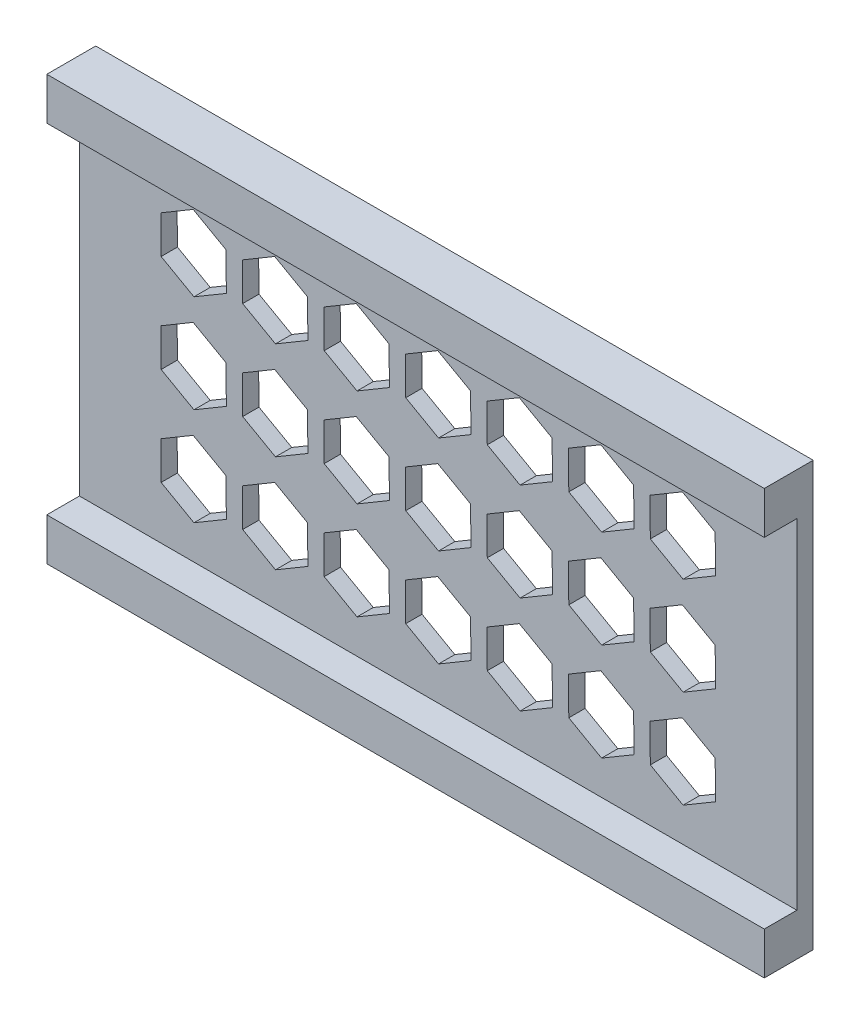
SolidWorks part; units mm, degrees
ref_plane "Front" through (0, 0, 0) normal (0, 0, 1) x (1, 0, 0)
ref_plane "Top" through (0, 0, 0) normal (0, 1, 0) x (1, 0, 0)
ref_plane "Right" through (0, 0, 0) normal (1, 0, 0) x (0, 0, -1)
sketch "Эскиз3" plane through (0, 0, 0) normal (0, 0, 1) x (1, 0, 0)
  line L0 (34.9411, 5.8743) -> (24.8833, 11.5464)
  line L1 (9.9411, 5.8743) -> (-0.1167, 11.5464)
  line L2 (110, -65) -> (-110, -65)
  line L3 (110, -65) -> (110, 65)
  line L4 (110, 65) -> (-110, 65)
  line L5 (-110, -65) -> (-110, 65)
  line L6 (110, -65) -> (-110, 65) construction
  line L7 (110, 65) -> (-110, -65) construction
  line L8 (-0.1167, 11.5464) -> (-10.0579, 5.6721)
  line L9 (-10.0579, 5.6721) -> (-9.9411, -5.8743)
  line L10 (-9.9411, -5.8743) -> (0.1167, -11.5464)
  line L11 (0.1167, -11.5464) -> (10.0579, -5.6721)
  line L12 (10.0579, -5.6721) -> (9.9411, 5.8743)
  line L13 (24.8833, 11.5464) -> (14.9421, 5.6721)
  line L14 (14.9421, 5.6721) -> (15.0589, -5.8743)
  line L15 (15.0589, -5.8743) -> (25.1167, -11.5464)
  line L16 (25.1167, -11.5464) -> (35.0579, -5.6721)
  line L17 (35.0579, -5.6721) -> (34.9411, 5.8743)
  line L18 (59.9411, 5.8743) -> (49.8833, 11.5464)
  line L19 (49.8833, 11.5464) -> (39.9421, 5.6721)
  line L20 (39.9421, 5.6721) -> (40.0589, -5.8743)
  line L21 (40.0589, -5.8743) -> (50.1167, -11.5464)
  line L22 (50.1167, -11.5464) -> (60.0579, -5.6721)
  line L23 (60.0579, -5.6721) -> (59.9411, 5.8743)
  line L24 (84.9411, 5.8743) -> (74.8833, 11.5464)
  line L25 (74.8833, 11.5464) -> (64.9421, 5.6721)
  line L26 (64.9421, 5.6721) -> (65.0589, -5.8743)
  line L27 (65.0589, -5.8743) -> (75.1167, -11.5464)
  line L28 (75.1167, -11.5464) -> (85.0579, -5.6721)
  line L29 (85.0579, -5.6721) -> (84.9411, 5.8743)
  line L30 (-15.0602, 5.8743) -> (-25.118, 11.5464)
  line L31 (-25.118, 11.5464) -> (-35.0591, 5.6721)
  line L32 (-35.0591, 5.6721) -> (-34.9424, -5.8743)
  line L33 (-34.9424, -5.8743) -> (-24.8845, -11.5464)
  line L34 (-24.8845, -11.5464) -> (-14.9434, -5.6721)
  line L35 (-14.9434, -5.6721) -> (-15.0602, 5.8743)
  line L36 (-40.0614, 5.8743) -> (-50.1193, 11.5464)
  line L37 (-50.1193, 11.5464) -> (-60.0604, 5.6721)
  line L38 (-60.0604, 5.6721) -> (-59.9437, -5.8743)
  line L39 (-59.9437, -5.8743) -> (-49.8858, -11.5464)
  line L40 (-49.8858, -11.5464) -> (-39.9447, -5.6721)
  line L41 (-39.9447, -5.6721) -> (-40.0614, 5.8743)
  line L42 (-65.0627, 5.8743) -> (-75.1206, 11.5464)
  line L43 (-75.1206, 11.5464) -> (-85.0617, 5.6721)
  line L44 (-85.0617, 5.6721) -> (-84.945, -5.8743)
  line L45 (-84.945, -5.8743) -> (-74.8871, -11.5464)
  line L46 (-74.8871, -11.5464) -> (-64.946, -5.6721)
  line L47 (-64.946, -5.6721) -> (-65.0627, 5.8743)
  line L48 (-65.0627, 35.8743) -> (-75.1206, 41.5464)
  line L49 (-75.1206, 41.5464) -> (-85.0617, 35.6721)
  line L50 (-85.0617, 35.6721) -> (-84.945, 24.1257)
  line L51 (-84.945, 24.1257) -> (-74.8871, 18.4536)
  line L52 (-74.8871, 18.4536) -> (-64.946, 24.3279)
  line L53 (-64.946, 24.3279) -> (-65.0627, 35.8743)
  line L54 (-40.0614, 35.8743) -> (-50.1193, 41.5464)
  line L55 (-50.1193, 41.5464) -> (-60.0604, 35.6721)
  line L56 (-60.0604, 35.6721) -> (-59.9437, 24.1257)
  line L57 (-59.9437, 24.1257) -> (-49.8858, 18.4536)
  line L58 (-49.8858, 18.4536) -> (-39.9447, 24.3279)
  line L59 (-39.9447, 24.3279) -> (-40.0614, 35.8743)
  line L60 (-15.0602, 35.8743) -> (-25.118, 41.5464)
  line L61 (-25.118, 41.5464) -> (-35.0591, 35.6721)
  line L62 (-35.0591, 35.6721) -> (-34.9424, 24.1257)
  line L63 (-34.9424, 24.1257) -> (-24.8845, 18.4536)
  line L64 (-24.8845, 18.4536) -> (-14.9434, 24.3279)
  line L65 (-14.9434, 24.3279) -> (-15.0602, 35.8743)
  line L66 (9.9411, 35.8743) -> (-0.1167, 41.5464)
  line L67 (-0.1167, 41.5464) -> (-10.0579, 35.6721)
  line L68 (-10.0579, 35.6721) -> (-9.9411, 24.1257)
  line L69 (-9.9411, 24.1257) -> (0.1167, 18.4536)
  line L70 (0.1167, 18.4536) -> (10.0579, 24.3279)
  line L71 (10.0579, 24.3279) -> (9.9411, 35.8743)
  line L72 (34.9411, 35.8743) -> (24.8833, 41.5464)
  line L73 (24.8833, 41.5464) -> (14.9421, 35.6721)
  line L74 (14.9421, 35.6721) -> (15.0589, 24.1257)
  line L75 (15.0589, 24.1257) -> (25.1167, 18.4536)
  line L76 (25.1167, 18.4536) -> (35.0579, 24.3279)
  line L77 (35.0579, 24.3279) -> (34.9411, 35.8743)
  line L78 (59.9411, 35.8743) -> (49.8833, 41.5464)
  line L79 (49.8833, 41.5464) -> (39.9421, 35.6721)
  line L80 (39.9421, 35.6721) -> (40.0589, 24.1257)
  line L81 (40.0589, 24.1257) -> (50.1167, 18.4536)
  line L82 (50.1167, 18.4536) -> (60.0579, 24.3279)
  line L83 (60.0579, 24.3279) -> (59.9411, 35.8743)
  line L84 (84.9411, 35.8743) -> (74.8833, 41.5464)
  line L85 (74.8833, 41.5464) -> (64.9421, 35.6721)
  line L86 (64.9421, 35.6721) -> (65.0589, 24.1257)
  line L87 (65.0589, 24.1257) -> (75.1167, 18.4536)
  line L88 (75.1167, 18.4536) -> (85.0579, 24.3279)
  line L89 (85.0579, 24.3279) -> (84.9411, 35.8743)
  line L90 (-40.0614, -24.1257) -> (-50.1193, -18.4536)
  line L91 (-50.1193, -18.4536) -> (-60.0604, -24.3279)
  line L92 (-60.0604, -24.3279) -> (-59.9437, -35.8743)
  line L93 (-59.9437, -35.8743) -> (-49.8858, -41.5464)
  line L94 (-49.8858, -41.5464) -> (-39.9447, -35.6721)
  line L95 (-39.9447, -35.6721) -> (-40.0614, -24.1257)
  line L96 (-15.0602, -24.1257) -> (-25.118, -18.4536)
  line L97 (-25.118, -18.4536) -> (-35.0591, -24.3279)
  line L98 (-35.0591, -24.3279) -> (-34.9424, -35.8743)
  line L99 (-34.9424, -35.8743) -> (-24.8845, -41.5464)
  line L100 (-24.8845, -41.5464) -> (-14.9434, -35.6721)
  line L101 (-14.9434, -35.6721) -> (-15.0602, -24.1257)
  line L102 (-65.0627, -24.1257) -> (-75.1206, -18.4536)
  line L103 (-75.1206, -18.4536) -> (-85.0617, -24.3279)
  line L104 (-85.0617, -24.3279) -> (-84.945, -35.8743)
  line L105 (-84.945, -35.8743) -> (-74.8871, -41.5464)
  line L106 (-74.8871, -41.5464) -> (-64.946, -35.6721)
  line L107 (-64.946, -35.6721) -> (-65.0627, -24.1257)
  line L108 (9.9411, -24.1257) -> (-0.1167, -18.4536)
  line L109 (-0.1167, -18.4536) -> (-10.0579, -24.3279)
  line L110 (-10.0579, -24.3279) -> (-9.9411, -35.8743)
  line L111 (-9.9411, -35.8743) -> (0.1167, -41.5464)
  line L112 (0.1167, -41.5464) -> (10.0579, -35.6721)
  line L113 (10.0579, -35.6721) -> (9.9411, -24.1257)
  line L114 (34.9411, -24.1257) -> (24.8833, -18.4536)
  line L115 (24.8833, -18.4536) -> (14.9421, -24.3279)
  line L116 (14.9421, -24.3279) -> (15.0589, -35.8743)
  line L117 (15.0589, -35.8743) -> (25.1167, -41.5464)
  line L118 (25.1167, -41.5464) -> (35.0579, -35.6721)
  line L119 (35.0579, -35.6721) -> (34.9411, -24.1257)
  line L120 (59.9411, -24.1257) -> (49.8833, -18.4536)
  line L121 (49.8833, -18.4536) -> (39.9421, -24.3279)
  line L122 (39.9421, -24.3279) -> (40.0589, -35.8743)
  line L123 (40.0589, -35.8743) -> (50.1167, -41.5464)
  line L124 (50.1167, -41.5464) -> (60.0579, -35.6721)
  line L125 (60.0579, -35.6721) -> (59.9411, -24.1257)
  line L126 (85.0579, -35.6721) -> (84.9411, -24.1257)
  line L127 (75.1167, -41.5464) -> (85.0579, -35.6721)
  line L128 (65.0589, -35.8743) -> (75.1167, -41.5464)
  line L129 (64.9421, -24.3279) -> (65.0589, -35.8743)
  line L130 (74.8833, -18.4536) -> (64.9421, -24.3279)
  line L131 (84.9411, -24.1257) -> (74.8833, -18.4536)
  line L132 (-40.0614, 5.8743) -> (-40.0614, -24.1257) construction
  line L133 (-110, 52) -> (110, 52)
  line L135 (0, 0) -> (110, 0) construction
  line L136 (-110, -52) -> (110, -52)
  circle A0 centre (0, 0) radius 10 construction
  point P1 (0, 0)
  point P6 (-9.9995, 29.8989)
  dimension "D3" = 20
  dimension "D1" = 220
  dimension "D2" = 130
  dimension "D4" = 11.5464
  dimension "D6" = 14.9987
  dimension "D8" = 15
  dimension "D10" = 9.9995
  dimension "D11" = 11.5464
  dimension "D12" = 64.6967
  dimension "D13" = 30
  dimension "D14" = 220
  dimension "D15" = 52
  dimension "D5" = 4
  dimension "D7" = 4
  dimension "D9" = 2
extrude "Бобышка-Вытянуть1" add sketch "Эскиз3" along normal blind 5 contours L5 L4 L3 L2
extrude "Вырез-Вытянуть1" cut sketch "Эскиз3<3>" along normal through all contours L28 L29 L24 L25 L26 L27 | L22 L23 L18 L19 L20 L21 | L124 L125 L120 L121 L122 L123 | L118 L119 L114 L115 L116 L117 | L16 L17 L0 L13 L14 L15 | L112 L113 L108 L109 L110 L111 | L100 L101 L96 L97 L98 L99 | L34 L35 L30 L31 L32 L33 | L11 L12 L1 L8 L9 L10 | L94 L95 L90 L91 L92 L93 | L40 L41 L36 L37 L38 L39 | L106 L107 L102 L103 L104 L105 | L52 L53 L48 L49 L50 L51 | L58 L59 L54 L55 L56 L57 | L64 L65 L60 L61 L62 L63 | L70 L71 L66 L67 L68 L69 | L76 L77 L72 L73 L74 L75 | L82 L83 L78 L79 L80 L81 | L88 L89 L84 L85 L86 L87 | L126 L131 L130 L129 L128 L127 | L46 L47 L42 L43 L44 L45 | L126 L131 L130 L129 L128 L127 | L47 L42 L43 L44 L45 L46 region at (25, 0, 0) region at (0, 0, 0) region at (50, 0, 0) region at (75, 0, 0) region at (-25.0013, 0, 0) region at (-50.0026, 0, 0) region at (-75.0038, 0, 0) region at (-75.0038, 30, 0) region at (-50.0026, 30, 0) region at (-25.0013, 30, 0) region at (0, 30, 0) region at (25, 30, 0) region at (50, 30, 0) region at (75, 30, 0) region at (-50.0026, -30, 0) region at (-25.0013, -30, 0) region at (-75.0038, -30, 0) region at (0, -30, 0) region at (25, -30, 0) region at (50, -30, 0) region at (75, -30, 0)
sketch "Эскиз3<3>" plane through (0, 0, 0) normal (0, 0, 1) x (1, 0, 0) same geometry as "Эскиз3"
extrude "Бобышка-Вытянуть2" add sketch "Эскиз3<4>" along normal blind 15 contours L5 L133 L3 L4 | L136 L5 L2 L3 region at (0, -58.5, 0) region at (0, 58.5, 0)
sketch "Эскиз3<4>" plane through (0, 0, 0) normal (0, 0, 1) x (1, 0, 0) same geometry as "Эскиз3"
